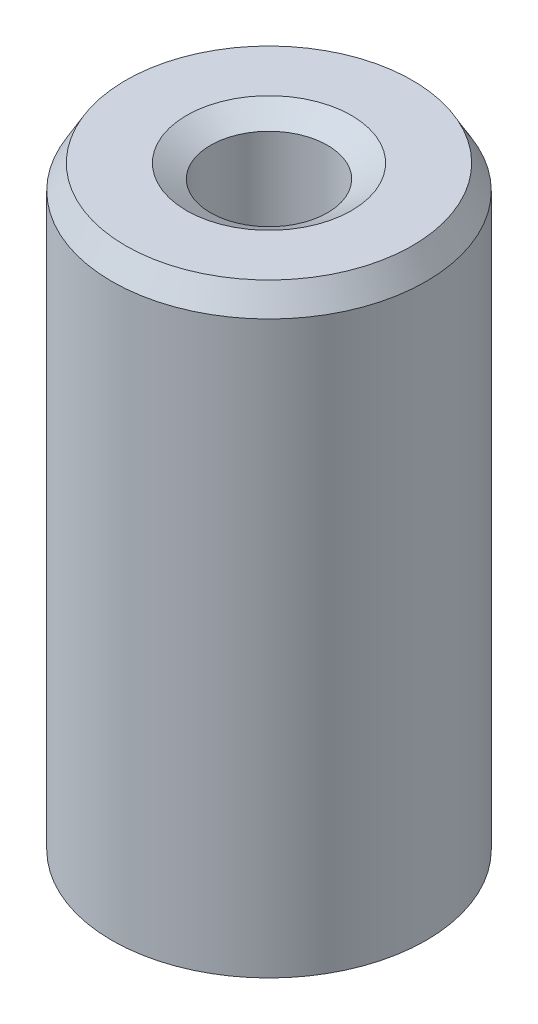
SolidWorks part; units mm, degrees
ref_plane "Front Plane" through (0, 0, 0) normal (0, 0, 1) x (1, 0, 0)
ref_plane "Top Plane" through (0, 0, 0) normal (0, 1, 0) x (1, 0, 0)
ref_plane "Right Plane" through (0, 0, 0) normal (1, 0, 0) x (0, 0, -1)
sketch "Sketch1" plane through (0, 0, 0) normal (0, 1, 0) x (1, 0, 0)
  circle A0 centre (0, 0) radius 15
  dimension "SLEEVE_OD" = 30
extrude "Boss-Extrude1" add sketch "Sketch1" along normal blind 58.0728
sketch "Sketch2" plane through (0, 0, 0) normal (0, 1, 0) x (1, 0, 0)
  circle A0 centre (0, 0) radius 5.5825
  dimension "BORE_D" = 11.1651
extrude "Cut-Extrude1" cut sketch "Sketch2" along normal through all
chamfer "Chamfer1" distance 2.2889 angle 30 4 edges at (0, 58.0728, 5.5825) (0, 0, 5.5825) (0, 0, 15) (0, 58.0728, 15) first distance on face at (0, 58.0728, 5.5825) first distance on face at (0, 0, 5.5825) first distance on face at (0, 58.0728, 15)
